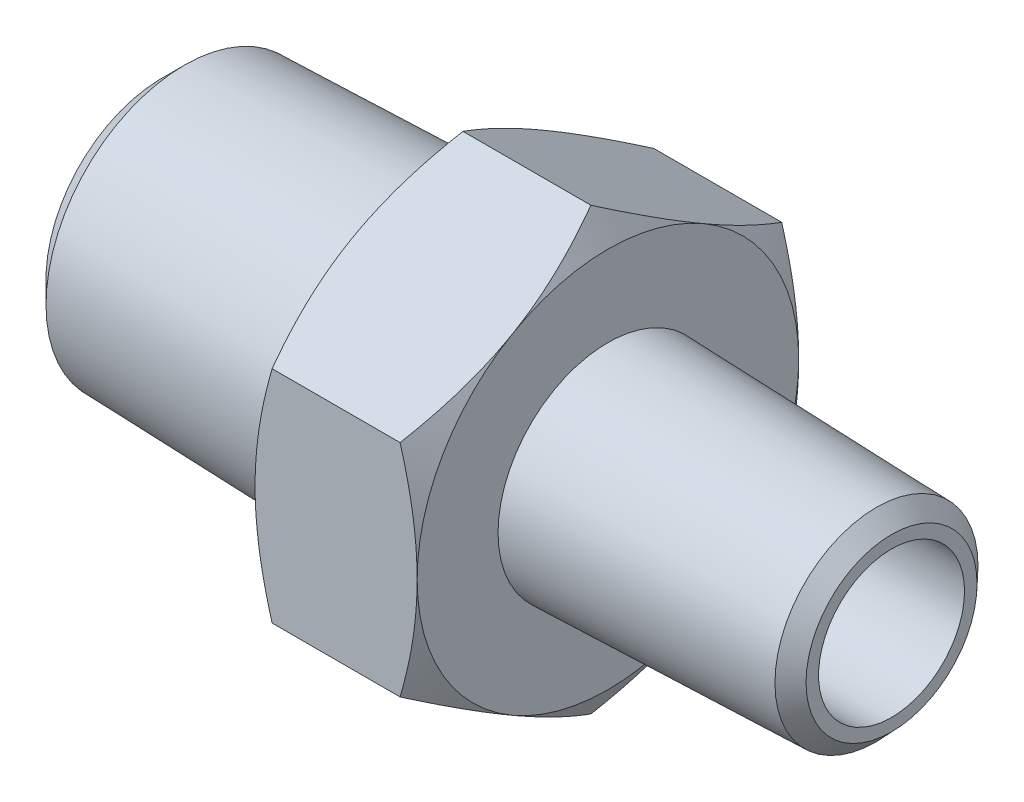
SolidWorks part; units mm, degrees
material "AISI 304"
ref_plane "Front Plane" through (0, 0, 0) normal (0, 0, 1) x (1, 0, 0)
ref_plane "Top Plane" through (0, 0, 0) normal (0, 1, 0) x (1, 0, 0)
ref_plane "Right Plane" through (0, 0, 0) normal (1, 0, 0) x (0, 0, -1)
sketch "Sketch1" plane through (0, 0, 0) normal (0, 0, 1) x (1, 0, 0)
  line L0 (-17.0656, 0) -> (17.0656, 0) construction
  line L1 (0, 8.9297) -> (0, -8.9297) construction
  line L2 (17.0656, 5.1435) -> (17.0656, -5.1435) construction
  line L3 (-17.0656, 6.858) -> (-17.0656, -6.858) construction
  line L4 (3.7924, 0) -> (-3.7924, 0) construction
  line L5 (17.0656, -4.7302) -> (3.7924, -5.1435) construction
  line L6 (-3.7924, -6.858) -> (-17.0656, -6.4447) construction
  point P9 (-3.7924, 0)
  point P10 (3.7924, 0)
  point P13 (11.145, -4.9146)
  point P17 (-11.145, -6.6291)
  dimension "Hex" = 17.8594
  dimension "length" = 34.1313
  dimension "pipe od" = 13.716
  dimension "pipe od 2" = 10.287
  dimension "D1" = 7.5847
  dimension "D2" = 13.2733
  dimension "D4" = 1.783
  dimension "D6" = 7.3526
  dimension "D7" = 1.783
  dimension "D5" = 7.3526
ref_plane "Plane1" through (-3.7924, 0, 0) normal (1, 0, 0) x (0, 0, -1)
sketch "Sketch2" plane through (-3.7924, 0, 0) normal (1, 0, 0) x (0, 0, -1)
  line L0 (0, 6.858) -> (0, -6.858) construction
  circle A0 centre (0, 0) radius 6.858
extrude "Extrude1" add sketch "Sketch2" against normal up to vertex (13.2733 mm away) draft 1.783 up to point (-17.0656, 0, 0)
chamfer "Chamfer1" distance 1.0026 angle 45 1 edges at (-17.0656, 0, -6.4447) first distance on face at (-17.0656, 0, -6.4447)
sketch "Sketch4" plane through (0, 0, 0) normal (0, 0, 1) x (1, 0, 0)
  line L0 (-4.3772, 6.858) -> (-3.2075, 6.858) construction
  line L1 (-4.3772, 6.858) -> (-3.8759, 5.895)
  line L2 (-3.8759, 5.895) -> (-3.7088, 5.895)
  line L3 (-3.7088, 5.895) -> (-3.2075, 6.858) construction
  line L4 (-4.1266, 6.3765) -> (-3.4582, 6.3765) construction
  line L5 (-3.7924, 5.895) -> (-3.7924, 6.858) construction
  line L6 (-4.3772, 6.858) -> (-3.1239, 7.0185)
  line L7 (-3.2075, 6.858) -> (-3.1239, 7.0185) construction
  line L10 (-3.1239, 7.0185) -> (-3.7924, 5.7345) construction
  line L11 (-3.7088, 5.895) -> (-3.1239, 7.0185)
  dimension "D1" = 55
  dimension "D2" = 0.1671
  dimension "D3" = 0.6684
ref_plane "Plane2" through (3.7924, 0, 0) normal (1, 0, 0) x (0, 0, -1)
sketch "Sketch5" plane through (3.7924, 0, 0) normal (1, 0, 0) x (0, 0, -1)
  line L0 (0, 5.1435) -> (0, -5.1435) construction
  circle A2 centre (0, 0) radius 5.1435
extrude "Extrude2" add sketch "Sketch5" along normal up to vertex (13.2733 mm away) draft 1.783 up to point (17.0656, 0, 0)
chamfer "Chamfer2" distance 0.7056 angle 45 1 edges at (17.0656, 0, -4.7302) first distance on face at (17.0656, 0, -4.7302)
sketch "Sketch7" plane through (0, 0, 0) normal (0, 0, 1) x (1, 0, 0)
  line L0 (3.3808, 5.1435) -> (3.7336, 4.5325) construction
  line L1 (3.7336, 4.5325) -> (3.8512, 4.5325)
  line L2 (3.8512, 4.5325) -> (4.2039, 5.1435)
  line L3 (3.3808, 5.1435) -> (4.2039, 5.1435) construction
  line L4 (3.7924, 5.1435) -> (3.7924, 4.5325) construction
  line L5 (3.5572, 4.838) -> (4.0275, 4.838) construction
  line L9 (3.7336, 4.5325) -> (3.322, 5.2453)
  line L10 (3.322, 5.2453) -> (3.7924, 4.4306) construction
  line L11 (3.322, 5.2453) -> (4.2039, 5.1435)
  dimension "D1" = 60
  dimension "D2" = 0.1176
  dimension "D3" = 0.4704
sketch "Sketch8" plane through (0, 0, 0) normal (0, 0, 1) x (1, 0, 0)
  line L0 (0, 6.858) -> (-3.7924, 6.858)
  line L1 (-3.7924, 6.858) -> (-10.4766, 5.067)
  line L2 (-10.4766, 5.067) -> (-10.4766, 0)
  line L3 (-10.4766, 0) -> (10.4766, 0)
  line L4 (10.4766, 0) -> (10.4766, 3.3525)
  line L5 (10.4766, 3.3525) -> (3.7924, 5.1435)
  line L6 (3.7924, 5.1435) -> (0, 5.1435)
  line L7 (0, 8.9297) -> (0, -8.9297) construction
  line L8 (0, 5.1435) -> (0, 6.858)
  dimension "D1" = 15
  dimension "D3" = 6.6842
  dimension "D2" = 15
revolve "Revolve1" add sketch "Sketch8" angle 360 about L0
sketch "Sketch9" plane through (0, 0, 0) normal (1, 0, 0) x (0, 0, -1)
  line L1 (0, 10.3111) -> (-8.9297, 5.1556)
  line L2 (-8.9297, 5.1556) -> (-8.9297, -5.1556)
  line L3 (-8.9297, -5.1556) -> (0, -10.3111)
  line L4 (0, -10.3111) -> (8.9297, -5.1556)
  line L5 (8.9297, -5.1556) -> (8.9297, 5.1556)
  line L6 (8.9297, 5.1556) -> (0, 10.3111)
  circle A0 centre (0, 0) radius 8.9297 construction
extrude "Extrude3" add sketch "Sketch9" against normal up to vertex (3.7924 mm away) and the other way up to vertex (3.7924 mm away) up to point (-3.7924, 0, 0) other way up to point (3.7924, 0, 0)
sketch "Sketch10" plane through (3.7924, 0, 0) normal (1, 0, 0) x (0, 0, -1)
  circle A0 centre (0, 0) radius 8.9297 construction
  circle A1 centre (0, 0) radius 8.9297
extrude "Cut-Extrude1" cut sketch "Sketch10" against normal through all draft 60 flip side to cut
sketch "Sketch11" plane through (-3.7924, 0, 0) normal (-1, 0, 0) x (0, 0, 1)
  circle A1 centre (0, 0) radius 8.9297
  circle A2 centre (0, 0) radius 8.9297
  dimension "D1" = 0
extrude "Cut-Extrude2" cut sketch "Sketch11" against normal through all draft 60 flip side to cut
sketch "Sketch12" plane through (-17.0656, 0, 0) normal (-1, 0, 0) x (0, 0, 1)
  circle A0 centre (0, 0) radius 4.6228
  dimension "D1" = 9.2456
extrude "Cut-Extrude3" cut sketch "Sketch12" against normal up to vertex (13.2733 mm away) up to point (-3.7924, 0, 8.9297)
sketch "Sketch13" plane through (17.0656, 0, 0) normal (1, 0, 0) x (0, 0, -1)
  circle A0 centre (0, 0) radius 3.4163
  dimension "D1" = 6.8326
extrude "Cut-Extrude4" cut sketch "Sketch13" against normal through all
sketch "Sketch14" plane through (-3.7924, 0, 0) normal (-1, 0, 0) x (0, 0, 1)
  circle A0 centre (0, 0) radius 4.6228 construction
  circle A1 centre (0, 0) radius 4.6228
extrude "Cut-Extrude5" cut sketch "Sketch14" against normal through all draft 41
equation "\"D1@Sketch1\" = \"length@Sketch1\"/4.5"
equation "\"D2@Sketch8\"= \"D1@Sketch8\""
